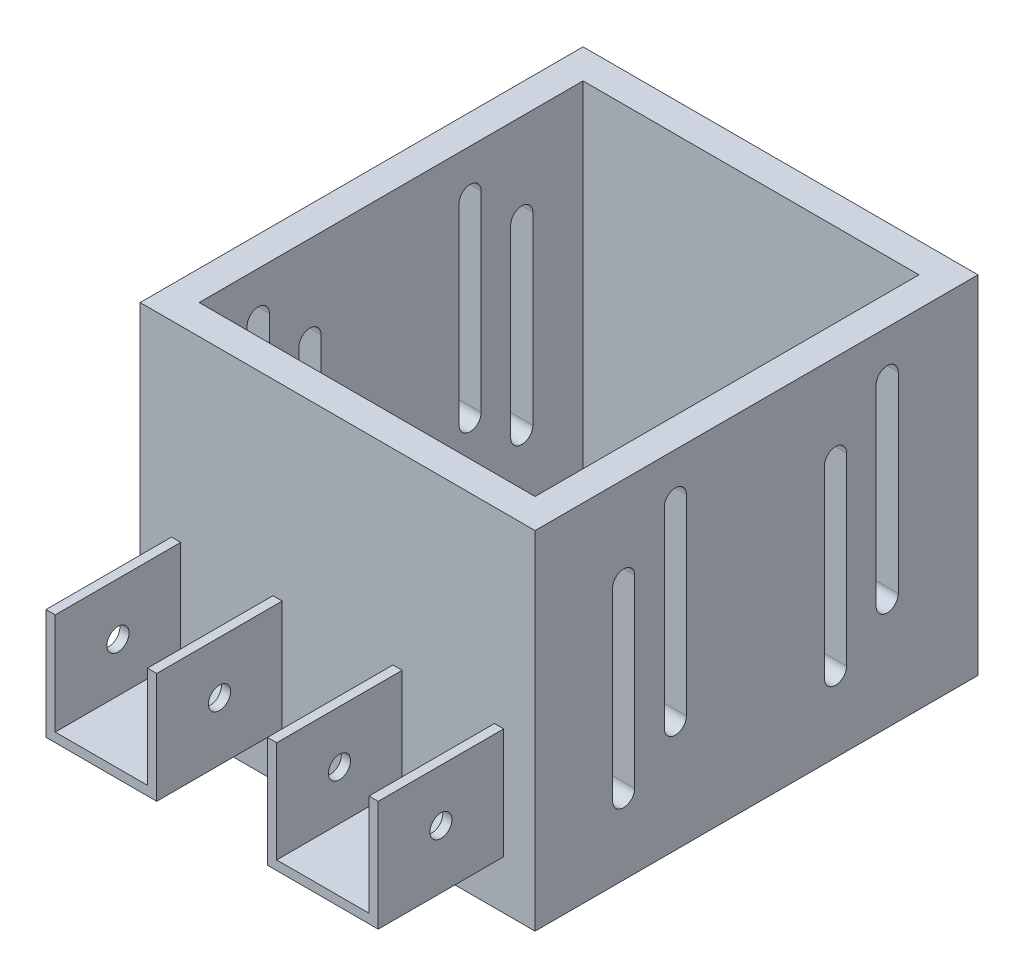
SolidWorks part; units mm, degrees
ref_plane "Front Plane" through (0, 0, 0) normal (0, 0, 1) x (1, 0, 0)
ref_plane "Top Plane" through (0, 0, 0) normal (0, 1, 0) x (1, 0, 0)
ref_plane "Right Plane" through (0, 0, 0) normal (1, 0, 0) x (0, 0, -1)
sketch "Sketch1" plane through (0, 0, 0) normal (0, 1, 0) x (1, 0, 0)
  line L1 (-26.75, 30) -> (26.75, 30)
  line L2 (-26.75, 30) -> (-26.75, -30)
  line L3 (-26.75, -30) -> (26.75, -30)
  line L4 (26.75, 30) -> (26.75, -30)
  line L5 (-26.75, 30) -> (26.75, -30) construction
  line L6 (-26.75, -30) -> (26.75, 30) construction
  line L7 (-22.75, 26) -> (22.75, 26)
  line L8 (-22.75, 26) -> (-22.75, -26)
  line L9 (-22.75, -26) -> (22.75, -26)
  line L10 (22.75, 26) -> (22.75, -26)
  line L11 (-22.75, 26) -> (22.75, -26) construction
  line L12 (-22.75, -26) -> (22.75, 26) construction
  point P0 (0, 0)
  point P6 (0, 0)
  dimension "D1" = 45.5
  dimension "D2" = 4
  dimension "D3" = 4
extrude "Boss-Extrude1" add sketch "Sketch1" along normal blind 47
sketch "Sketch3" plane through (-26.75, 0, 0) normal (-1, 0, 0) x (0, 0, 1)
  line L0 (-30, 47) -> (30, 47) construction
  line L1 (18, 15) -> (18, 41) construction
  line L2 (16.5, 15) -> (16.5, 41)
  line L3 (19.5, 15) -> (19.5, 41)
  line L4 (-30, 0) -> (30, 0) construction
  line L5 (11, 35) -> (11, 10) construction
  line L6 (12.5, 35) -> (12.5, 10)
  line L7 (9.5, 35) -> (9.5, 10)
  arc A2 (16.5, 15) -> (19.5, 15) centre (18, 15) ccw
  arc A3 (19.5, 41) -> (16.5, 41) centre (18, 41) ccw
  arc A4 (12.5, 35) -> (9.5, 35) centre (11, 35) ccw
  arc A5 (9.5, 10) -> (12.5, 10) centre (11, 10) ccw
  point P7 (11, 22.5)
  point P9 (18, 28)
  point P19 (0, 0)
  point P20 (0, 0)
  dimension "D1" = 8
  dimension "D3" = 3
  dimension "D2" = 15
  dimension "D4" = 6
  dimension "D5" = 7
  dimension "D6" = 12
  dimension "D7" = 3
  dimension "D8" = 10
extrude "Cut-Extrude1" cut sketch "Sketch3" against normal blind 4 and the other way through all
pattern_linear "LPattern1" count 2 spacing 28.7 along (0, 0, -1) of "Cut-Extrude1"
sketch "Sketch9" plane through (26.75, 0, 0) normal (1, 0, 0) x (0, 0, -1)
  line L0 (-18, 35) -> (-18, 10) construction
  line L1 (-16.5, 35) -> (-16.5, 10)
  line L2 (-19.5, 35) -> (-19.5, 10)
  line L3 (-30, 47) -> (30, 47) construction
  line L4 (-30, 0) -> (30, 0) construction
  line L5 (-11, 41) -> (-11, 15) construction
  line L6 (-9.5, 41) -> (-9.5, 15)
  line L7 (-12.5, 41) -> (-12.5, 15)
  arc A0 (-16.5, 35) -> (-19.5, 35) centre (-18, 35) ccw
  arc A1 (-19.5, 10) -> (-16.5, 10) centre (-18, 10) ccw
  arc A2 (-9.5, 41) -> (-12.5, 41) centre (-11, 41) ccw
  arc A3 (-12.5, 15) -> (-9.5, 15) centre (-11, 15) ccw
  point P2 (-18, 22.5)
  point P14 (-11, 28)
  point P19 (0, 0)
  dimension "D1" = 8
  dimension "D2" = 3
  dimension "D3" = 12
  dimension "D4" = 10
  dimension "D5" = 6
  dimension "D6" = 3
  dimension "D7" = 7
  dimension "D8" = 15
extrude "Cut-Extrude4" cut sketch "Sketch9" against normal up to surface (4 mm away) up to face at (22.75, 23.5, 0)
pattern_linear "LPattern2" count 2 spacing 28.7 along (0, 0, -1) of "Cut-Extrude4"
sketch "Sketch5" plane through (0, 0, 30) normal (0, 0, 1) x (1, 0, 0)
  line L0 (26.75, 47) -> (26.75, 0) construction
  line L2 (-22.5, 21.61) -> (-22.5, 6.61)
  line L3 (-22.5, 6.61) -> (-7.5, 6.61)
  line L4 (-7.5, 21.61) -> (-7.5, 6.61)
  line L8 (7.5, 21.61) -> (7.5, 6.61)
  line L9 (7.5, 6.61) -> (22.5, 6.61)
  line L10 (22.5, 21.61) -> (22.5, 6.61)
  line L13 (-26.75, 0) -> (26.75, 0) construction
  line L14 (-26.75, 47) -> (-26.75, 0) construction
  line L16 (8.75, 20.36) -> (8.75, 21.61)
  line L17 (8.75, 20.36) -> (8.75, 7.86)
  line L18 (8.75, 7.86) -> (21.25, 7.86)
  line L19 (21.25, 20.36) -> (21.25, 7.86)
  line L23 (-21.25, 20.36) -> (-21.25, 7.86)
  line L24 (-21.25, 7.86) -> (-8.75, 7.86)
  line L25 (-8.75, 20.36) -> (-8.75, 7.86)
  line L28 (8.75, 21.61) -> (7.5, 21.61)
  line L29 (21.25, 20.36) -> (21.25, 21.61)
  line L30 (21.25, 21.61) -> (22.5, 21.61)
  line L31 (-21.25, 20.36) -> (-21.25, 21.61)
  line L32 (-21.25, 21.61) -> (-22.5, 21.61)
  line L33 (-8.75, 20.36) -> (-8.75, 21.61)
  line L34 (-8.75, 21.61) -> (-7.5, 21.61)
  point P0 (-15, 14.11)
  point P5 (15, 14.11)
  point P16 (-15, 14.11)
  point P18 (15, 14.11)
  dimension "D1" = 4.25
  dimension "D2" = 4.25
  dimension "D3" = 15
  dimension "D5" = 12.5
  dimension "D4" = 6.61
extrude "Boss-Extrude2" add sketch "Sketch5" along normal blind 17
sketch "Sketch10" plane through (22.5, 0, 0) normal (1, 0, 0) x (0, 0, -1)
  line L0 (-47, 6.61) -> (-30, 6.61) construction
  line L1 (-47, 6.61) -> (-47, 21.61) construction
  circle A0 centre (-38.5, 14.51) radius 1.5
  dimension "D1" = 3
  dimension "D2" = 7.9
  dimension "D3" = 8.5
extrude "Cut-Extrude5" cut sketch "Sketch10" against normal through all
equation "\"var1\"=4.25"
equation "\"D1@Sketch5\"=\"var1\""
equation "\"D2@Sketch5\"=\"var1\""
